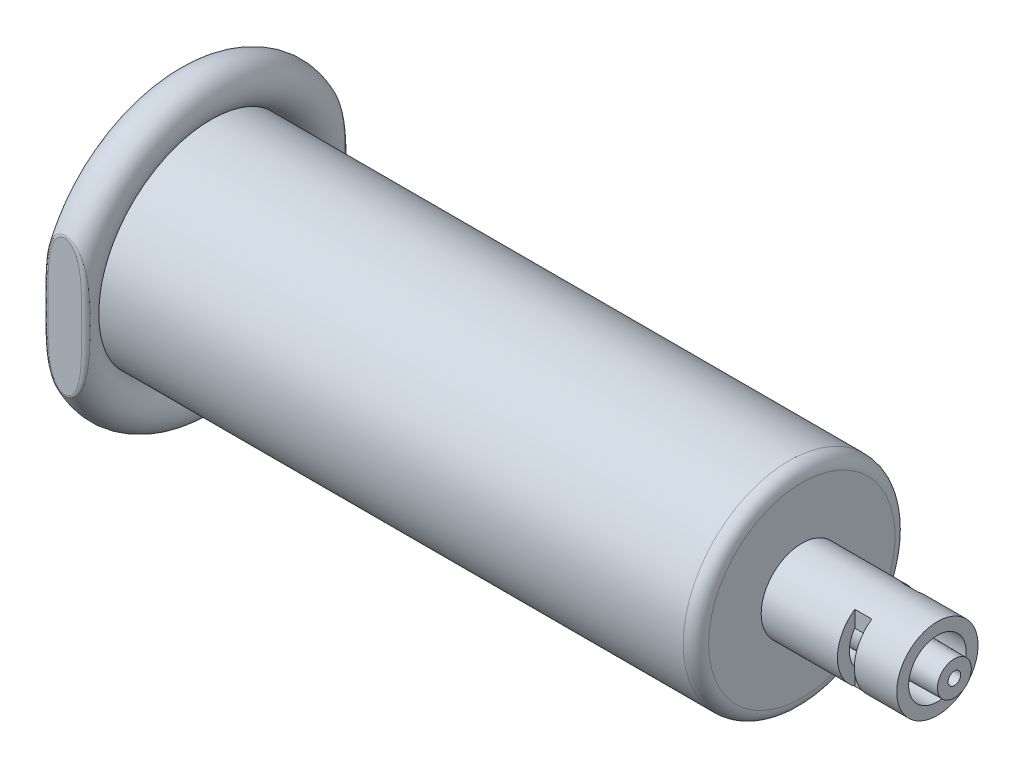
SolidWorks part; units mm, degrees
material "Glass"
ref_plane "Front Plane" through (0, 0, 0) normal (0, 0, 1) x (1, 0, 0)
ref_plane "Top Plane" through (0, 0, 0) normal (0, 1, 0) x (1, 0, 0)
ref_plane "Right Plane" through (0, 0, 0) normal (1, 0, 0) x (0, 0, -1)
sketch "Sketch1" plane through (0, 0, 0) normal (0, 0, 1) x (1, 0, 0)
  line L0 (72.5, 12.5) -> (2.5, 12.5)
  line L1 (0, 15) -> (0, 0) construction
  line L2 (74, 11) -> (74, 4.8)
  line L3 (74, 4.8) -> (90, 4.8)
  line L4 (90, 4.8) -> (90, 2) construction
  line L5 (90, 2) -> (92, 2) construction
  line L6 (92, 2) -> (92, 0.75)
  line L7 (92, 0.75) -> (74, 0.75)
  line L8 (92, 2) -> (74, 2.225)
  line L9 (74, 2.225) -> (74, 3.4)
  line L10 (74, 3.4) -> (90, 3.4)
  line L11 (90, 3.4) -> (90, 4.8) construction
  line L12 (90, 4.8) -> (90, 3.4)
  line L13 (0, 15) -> (0, 10)
  line L14 (0, 10) -> (71, 10)
  line L15 (71, 10) -> (73, 8)
  line L16 (73, 8) -> (73, 0.75)
  line L17 (73, 0.75) -> (74, 0.75)
  line L18 (0, 0) -> (172, 0) construction
  arc A0 (2.5, 12.5) -> (0, 15) centre (2.5, 15) ccw
  arc A1 (72.5, 12.5) -> (74, 11) centre (72.5, 11) cw
  dimension "D1" = 2.5
  dimension "D7" = 1.5
  dimension "D2" = 70
  dimension "D3" = 12.5
  dimension "D4" = 2
  dimension "D5" = 0.75
  dimension "D6" = 4.8
  dimension "D8" = 16
  dimension "D9" = 2
  dimension "D10" = 2.225
  dimension "D11" = 10
  dimension "D12" = 45
  dimension "D13" = 2
  dimension "D14" = 1
revolve "Revolve1" add sketch "Sketch1" angle 360 about L18
sketch "Sketch2" plane through (0, 0, 0) normal (-1, 0, 0) x (0, 0, 1)
  line L1 (-15.5, 19) -> (15.5, 19)
  line L2 (-15.5, 19) -> (-15.5, -19)
  line L3 (-15.5, -19) -> (15.5, -19)
  line L4 (15.5, 19) -> (15.5, -19)
  line L5 (-21.8513, 21.9925) -> (22.1336, 21.9925)
  line L6 (-21.8513, 21.9925) -> (-21.8513, -23.6299)
  line L7 (-21.8513, -23.6299) -> (22.1336, -23.6299)
  line L8 (22.1336, 21.9925) -> (22.1336, -23.6299)
  point P4 (0, 19)
  point P6 (15.5, 0)
  dimension "D1" = 31
  dimension "D2" = 38
extrude "Cut-Extrude1" cut sketch "Sketch2" against normal blind 10 contours L8 L5 L6 L7 L1 L4 L3 L2 region at (0, 21.3587, 0.1412)
fillet "Fillet1" radius 0.5 2 edges at (0.0541, 0.728, -15.5) (4.9459, -0.728, 15.5)
sketch "Sketch3" plane through (0, 0, 0) normal (0, 1, 0) x (1, 0, 0)
  line L0 (74, 0) -> (92, 0) construction
  line L1 (83, 8.75) -> (85, 8.75)
  line L2 (83, 8.75) -> (83, 2.75)
  line L3 (83, 2.75) -> (85, 2.75)
  line L4 (85, 8.75) -> (85, 2.75)
  line L5 (83, -2.75) -> (85, -2.75)
  line L6 (83, -2.75) -> (83, -8.75)
  line L7 (83, -8.75) -> (85, -8.75)
  line L8 (85, -2.75) -> (85, -8.75)
  line L9 (74, -4.8) -> (74, 4.8) construction
  line L10 (92, -2) -> (92, 2) construction
  line L11 (90, -4.8) -> (90, 4.8) construction
  line L12 (83, 2.75) -> (83, -2.75) construction
  point P14 (83, 0)
  dimension "D1" = 5
  dimension "D2" = 2
  dimension "D3" = 5.5
  dimension "D4" = 6
extrude "Cut-Extrude2" cut sketch "Sketch3" against normal through all both and the other way through all
